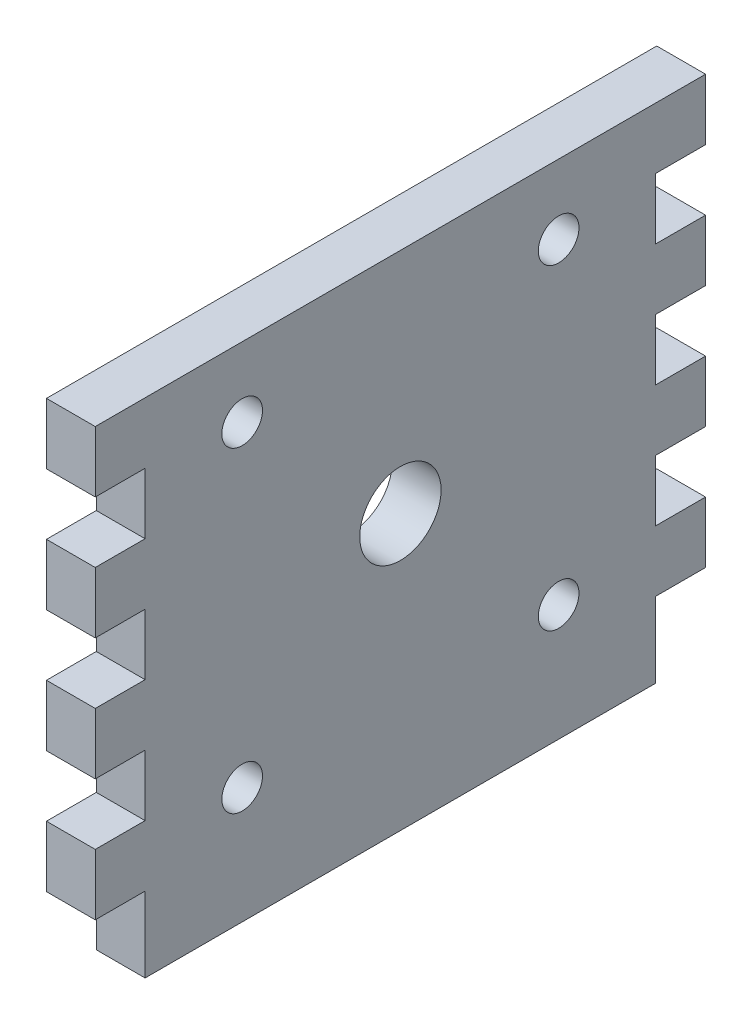
SolidWorks part; units mm, degrees
material "Thornel VCB-20 Carbon Cloth"
ref_plane "Front Plane" through (0, 0, 0) normal (0, 0, 1) x (1, 0, 0)
ref_plane "Top Plane" through (0, 0, 0) normal (0, 1, 0) x (1, 0, 0)
ref_plane "Right Plane" through (0, 0, 0) normal (1, 0, 0) x (0, 0, -1)
sketch "Sketch1" plane through (0, 0, 0) normal (1, 0, 0) x (0, 0, -1)
  line L1 (-36.7425, 26.5162) -> (39.4575, 26.5162)
  line L2 (-36.7425, 26.5162) -> (-36.7425, -36.2218)
  line L3 (-36.7425, -36.2218) -> (39.4575, -36.2218)
  line L4 (39.4575, 26.5162) -> (39.4575, -36.2218)
  dimension "D1" = 76.2
  dimension "D2" = 62.738
extrude "Boss-Extrude1" add sketch "Sketch1" along normal blind 6.096
sketch "Sketch2" plane through (6.096, 0, 0) normal (1, 0, 0) x (0, 0, -1)
  line L0 (-18.3991, 17.8247) -> (1.3575, -1.9318) construction
  line L2 (1.3575, -1.9318) -> (1.3575, 17.7349) construction
  line L3 (1.3575, 17.7349) -> (1.3575, -22.7612) construction
  line L4 (1.3575, -1.9318) -> (25.6979, -1.9318) construction
  line L5 (25.6979, -1.9318) -> (-22.0212, -1.9318) construction
  line L6 (1.3575, -1.9318) -> (21.114, 17.8247) construction
  line L7 (1.3575, -1.9318) -> (21.114, -21.6884) construction
  line L8 (1.3575, -1.9318) -> (-18.3991, -21.6884) construction
  line L9 (-36.7425, 26.5162) -> (-36.7425, -36.2218) construction
  line L10 (-36.7425, -36.2218) -> (39.4575, -36.2218) construction
  circle A0 centre (1.3575, -1.9318) radius 5.08
  circle A1 centre (-18.3991, 17.8247) radius 2.54
  circle A2 centre (21.114, 17.8247) radius 2.54
  circle A3 centre (21.114, -21.6884) radius 2.54
  circle A4 centre (-18.3991, -21.6884) radius 2.54
  dimension "D1" = 27.94
  dimension "D2" = 45
  dimension "D3" = 27.94
  dimension "D4" = 45
  dimension "D5" = 45
  dimension "D6" = 45
  dimension "D7" = 27.94
  dimension "D8" = 27.94
  dimension "D9" = 38.1
  dimension "D10" = 34.29
extrude "Cut-Extrude1" cut sketch "Sketch2" against normal up to surface (6.096 mm away) up to face at (0, -4.8528, -1.3575)
sketch "Sketch3" plane through (6.096, 0, 0) normal (1, 0, 0) x (0, 0, -1)
  line L0 (-36.7425, 18.8962) -> (-30.5195, 18.8962)
  line L1 (-36.7425, 26.5162) -> (-36.7425, -36.2218) construction
  line L2 (-30.5195, 18.8962) -> (-30.5195, 11.2762)
  line L4 (-30.5195, 11.2762) -> (-36.7425, 11.2762)
  line L9 (39.4575, 26.5162) -> (-36.7425, 26.5162) construction
  line L10 (-36.7425, 3.6562) -> (-30.5195, 3.6562)
  line L11 (-30.5195, 3.6562) -> (-30.5195, -3.9638)
  line L12 (-30.5195, -3.9638) -> (-36.7425, -3.9638)
  line L17 (-36.7425, -11.5838) -> (-30.5195, -11.5838)
  line L18 (-30.5195, -11.5838) -> (-30.5195, -19.2038)
  line L19 (-30.5195, -19.2038) -> (-36.7425, -19.2038)
  line L23 (1.3575, -1.9318) -> (1.3575, -36.2218) construction
  line L24 (-36.7425, -36.2218) -> (39.4575, -36.2218) construction
  line L25 (1.3575, -36.2218) -> (1.3575, 26.5162) construction
  line L26 (-36.7425, 18.8962) -> (-36.7425, 11.2762)
  line L27 (-36.7425, 3.6562) -> (-36.7425, -3.9638)
  line L29 (33.2345, -19.2038) -> (39.4575, -19.2038)
  line L30 (33.2345, -11.5838) -> (33.2345, -19.2038)
  line L31 (39.4575, -11.5838) -> (33.2345, -11.5838)
  line L32 (-36.7425, -11.5838) -> (-36.7425, -19.2038)
  line L34 (39.4575, 18.8962) -> (39.4575, 11.2762)
  line L36 (33.2345, -3.9638) -> (39.4575, -3.9638)
  line L37 (33.2345, 3.6562) -> (33.2345, -3.9638)
  line L38 (39.4575, 3.6562) -> (33.2345, 3.6562)
  line L41 (39.4575, 3.6562) -> (39.4575, -3.9638)
  line L43 (33.2345, 11.2762) -> (39.4575, 11.2762)
  line L44 (39.4575, -11.5838) -> (39.4575, -19.2038)
  line L45 (33.2345, 18.8962) -> (33.2345, 11.2762)
  line L46 (39.4575, 18.8962) -> (33.2345, 18.8962)
  dimension "D1" = 7.62
  dimension "0.245" = 6.223
  dimension "D3" = 7.62
  dimension "D4" = 7.62
  dimension "D5" = 3
extrude "Cut-Extrude2" cut sketch "Sketch3" against normal up to surface (6.096 mm away) up to face at (0, -21.6884, 15.8591)
sketch "Sketch4" plane through (6.096, 0, 0) normal (1, 0, 0) x (0, 0, -1)
  line L5 (-36.7425, -36.2218) -> (-30.5195, -36.2218)
  line L6 (-36.7425, -36.2218) -> (-36.7425, -26.8238)
  line L7 (-36.7425, -26.8238) -> (-30.5195, -26.8238)
  line L8 (-30.5195, -36.2218) -> (-30.5195, -26.8238)
  line L9 (1.3575, -1.9318) -> (1.3575, 30.0478)
  line L10 (1.3575, 30.0478) -> (1.3575, -34.4123)
  line L11 (33.2345, -36.2218) -> (33.2345, -26.8238)
  line L12 (39.4575, -26.8238) -> (33.2345, -26.8238)
  line L13 (39.4575, -36.2218) -> (39.4575, -26.8238)
  line L14 (39.4575, -36.2218) -> (33.2345, -36.2218)
  line M21 (-36.7425, -36.2218) -> (39.4575, -36.2218)
  line M22 (39.4575, -36.2218) -> (39.4575, -19.2038)
  dimension "D1" = 6.223
  dimension "D2" = 9.398
extrude "Cut-Extrude3" cut sketch "Sketch4" against normal up to surface (6.096 mm away) and the other way blind 7.874 contours L12 L11 M22 M21 | L7 L8 L5 L6 region at (6.096, -31.5228, -36.346) up to face at (0, -0.8251, -1.3575)
